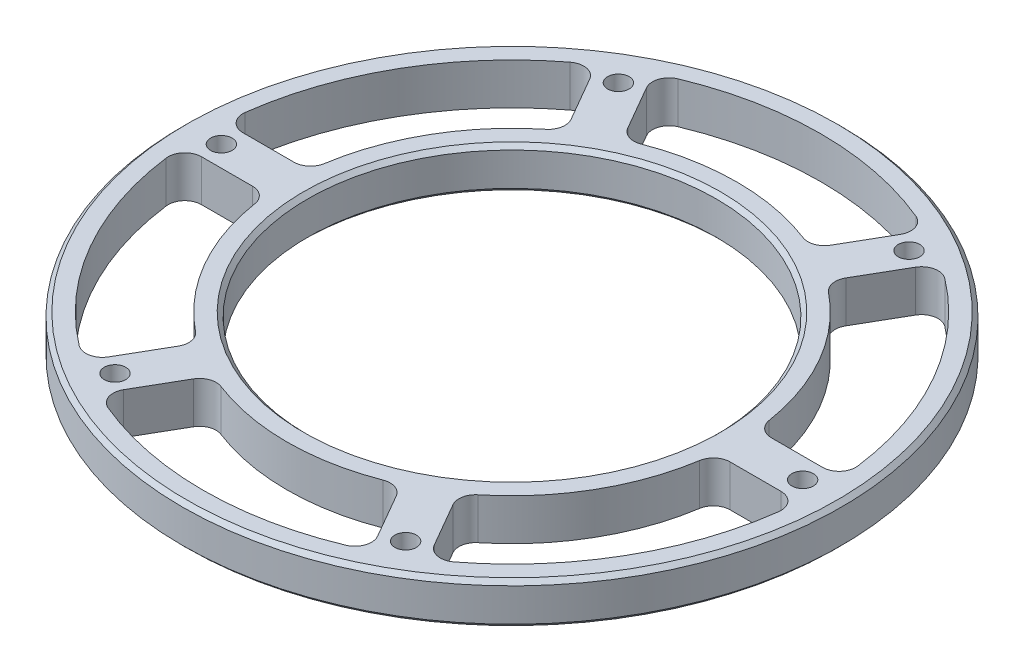
SolidWorks part; units mm, degrees
material "6061-T6 (SS)"
ref_plane "Front Plane" through (0, 0, 0) normal (0, 0, 1) x (1, 0, 0)
ref_plane "Top Plane" through (0, 0, 0) normal (0, 1, 0) x (1, 0, 0)
ref_plane "Right Plane" through (0, 0, 0) normal (1, 0, 0) x (0, 0, -1)
sketch "Sketch2" plane through (0, 0, 0) normal (1, 0, 0) x (0, 0, -1)
  line L0 (-49.2125, 0) -> (-79.375, 0)
  line L1 (-79.375, 0) -> (-79.375, 10)
  line L2 (-79.375, 10) -> (-49.2125, 10)
  line L3 (-49.2125, 10) -> (-49.2125, 0)
  dimension "D1" = 79.375
  dimension "D2" = 10
  dimension "D4" = 49.2125
ref_axis "Axis1" through (0, -0.5, 0) along (0, 1, 0)
revolve "Revolve1" add sketch "Sketch2" angle 360 about axis through (0, -0.5, 0) along (0, 1, 0)
hole_wizard "#6 (0.204) Diameter Hole1" positions "Sketch6" profile "Sketch7" hole size "#6" standard "ANSI Inch" end condition through all
sketch "Sketch6" plane through (0, 10, 0) normal (0, 1, 0) x (1, 0, 0)
  line L0 (0, 0) -> (-69.8201, 120.932) construction
  line L2 (0, 0) -> (0, 109.0908) construction
  point P0 (-35, 60.6218)
  dimension "D1" = 30
  dimension "D2" = 70
sketch "Sketch7" plane through (-35, 10, -60.6218) normal (1, 0, 0) x (0, 0, 1)
  line L0 (0, 0) -> (0, 10)
  line L1 (0, 10) -> (2.5908, 10)
  line L2 (2.5908, 10) -> (2.5908, 0)
  line L5 (2.5908, 0) -> (0, 0)
  line L11 (0, -6.35) -> (0, 107.95) construction
  dimension "Thru Hole Dia." = 5.1816
  dimension "Thru Hole Depth" = 10
pattern_circular "CirPattern3" count 6 over 360 about axis through (0, -0.5, 0) along (0, 1, 0) of "#6 (0.204) Diameter Hole1"
sketch "Sketch8" plane through (0, 10, 0) normal (0, 1, 0) x (1, 0, 0)
  line L4 (0, 0) -> (0, 93.9995) construction
  line L5 (-22.6606, 49.2493) -> (-32.7732, 66.7649)
  line L6 (22.6606, 49.2493) -> (32.7732, 66.7649)
  line L7 (0, 0) -> (-35, 60.6218) construction
  arc A0 (-22.6606, 49.2493) -> (22.6606, 49.2493) centre (0, 0) cw
  arc A1 (-32.7732, 66.7649) -> (32.7732, 66.7649) centre (0, 0) cw
  circle A2 centre (0, 0) radius 79.375 construction
  circle A4 centre (0, 0) radius 49.2125 construction
  dimension "D1" = 5
  dimension "D2" = 5
  dimension "D3" = 5
extrude "Cut-Extrude1" cut sketch "Sketch8" against normal through all
fillet "Fillet1" radius 4 4 edges at (-22.6606, 5, -49.2493) (22.6606, 5, -49.2493) (32.7732, 5, -66.7649) (-32.7732, 5, -66.7649)
pattern_circular "CirPattern4" count 6 over 360 about axis through (0, -0.5, 0) along (0, 1, 0) of "Cut-Extrude1", "Fillet1"
chamfer "Chamfer1" distance 1 angle 45 2 edges at (0, 10, -49.2125) (0, 0, -49.2125)
chamfer "Chamfer2" distance 1 angle 45 2 edges at (0, 10, -79.375) (0, 0, -79.375)
equation "\"TubeDiameter\" = 6.250in"
equation "\"D1@Sketch2\"=\"TubeDiameter\"/2"
